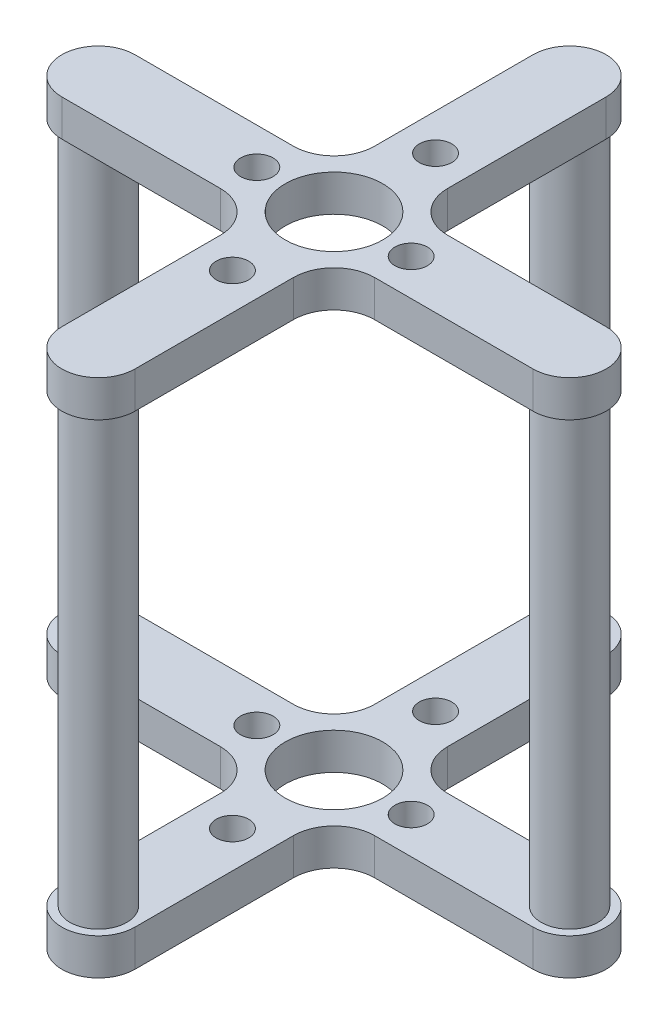
SolidWorks part; units mm, degrees
ref_plane "Front Plane" through (0, 0, 0) normal (0, 0, 1) x (1, 0, 0)
ref_plane "Top Plane" through (0, 0, 0) normal (0, 1, 0) x (1, 0, 0)
ref_plane "Right Plane" through (0, 0, 0) normal (1, 0, 0) x (0, 0, -1)
sketch "Sketch1" plane through (0, 0, 0) normal (0, 1, 0) x (1, 0, 0)
  line L0 (0, 29) -> (0, -29) construction
  line L1 (4.5, 29) -> (4.5, -29)
  line L2 (-4.5, 29) -> (-4.5, -29)
  line L3 (29, 0) -> (-29, 0) construction
  line L4 (29, -4.5) -> (-29, -4.5)
  line L5 (29, 4.5) -> (-29, 4.5)
  arc A0 (4.5, 29) -> (-4.5, 29) centre (0, 29) ccw
  arc A1 (-4.5, -29) -> (4.5, -29) centre (0, -29) ccw
  arc A2 (29, -4.5) -> (29, 4.5) centre (29, 0) ccw
  arc A3 (-29, 4.5) -> (-29, -4.5) centre (-29, 0) ccw
  point P2 (0, 0)
  point P13 (0, 0)
  point P18 (0, 0)
  dimension "D2" = 4.5
  dimension "D1" = 58
  dimension "D3" = 2
extrude "Boss-Extrude1" add sketch "Sketch1" along normal blind 4.5 contours L5 A3 L4 L2 | L4 A2 L5 L1 | L2 A1 L1 A0 region at (18.5351, 0, 0) region at (-18.5351, 0, 0)
sketch "Sketch2" plane through (0, 4.5, 0) normal (0, 1, 0) x (1, 0, 0)
  line L0 (0, 0) -> (-16.2785, 0) construction
  line L1 (0, 0) -> (0, 10.6488) construction
  circle A0 centre (0, 0) radius 6
  circle A1 centre (9.5, 0) radius 2
  circle A2 centre (29, 0) radius 3.5
  circle A3 centre (0, 12.5) radius 2
  circle A4 centre (0, -29) radius 3.5
  circle A5 centre (-29, 0) radius 3.5
  circle A6 centre (0, 29) radius 3.5
  circle A7 centre (-9.5, 0) radius 2
  circle A8 centre (0, -12.5) radius 2
  point P19 (0, 0)
  dimension "D1" = 12
  dimension "D2" = 4
  dimension "D3" = 7
  dimension "D4" = 4
  dimension "D5" = 9.5
  dimension "D6" = 12.5
  dimension "D7" = 4
extrude "Cut-Extrude1" cut sketch "Sketch2" against normal through all
fillet "Fillet1" radius 5 4 edges at (-4.5, 2.25, 4.5) (4.5, 2.25, 4.5) (4.5, 2.25, -4.5) (-4.5, 2.25, -4.5)
sketch "Sketch4" plane through (0, 0, 0) normal (0, -1, 0) x (1, 0, 0)
  circle A0 centre (0, -29) radius 3.5
  circle A1 centre (-29, 0) radius 3.5
  circle A2 centre (0, 29) radius 3.5
  circle A3 centre (29, 0) radius 3.5
  point P12 (0, 0)
  dimension "D1" = 7
  dimension "D2" = 4
extrude "Boss-Extrude2" add sketch "Sketch4" along normal blind 27.5 and the other way blind 4.5
ref_plane "Plane1" through (0, -25, 0) normal (0, 1, 0) x (1, 0, 0)
mirror "Mirror2" about plane through (0, -27.5, 29) normal (0, -1, 0) of bodies 103
